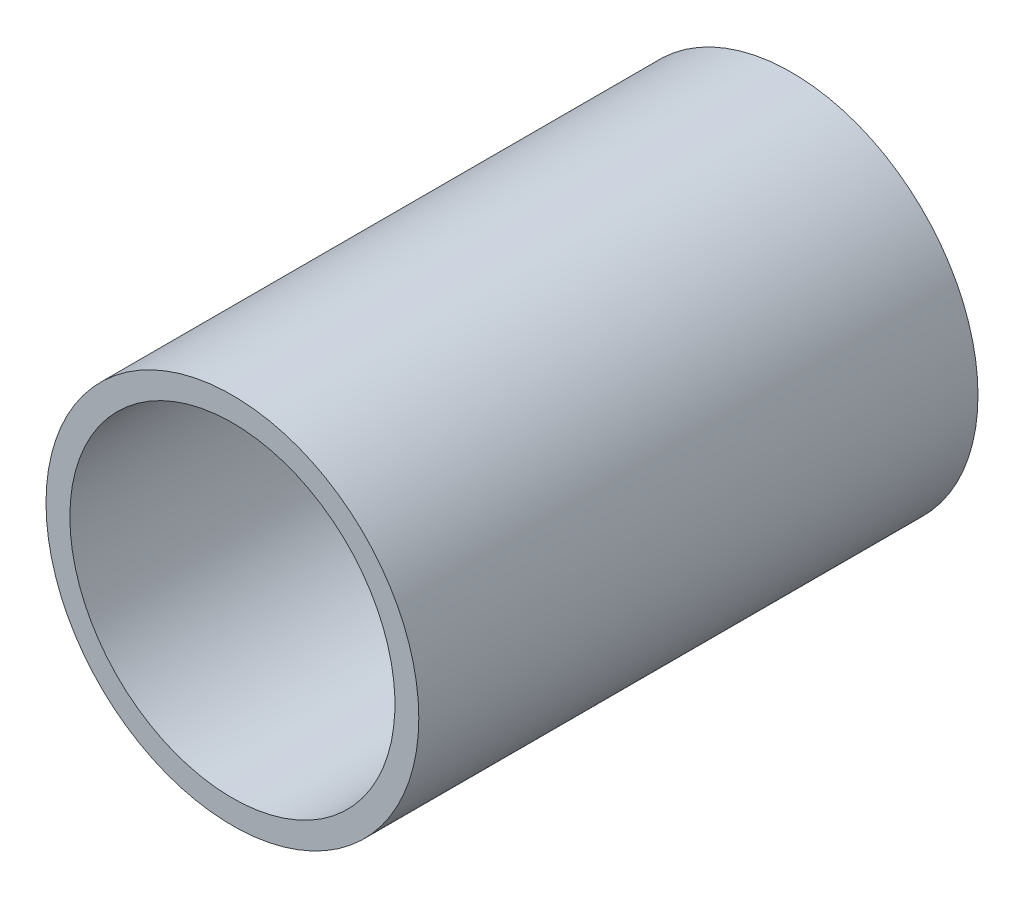
SolidWorks part; units mm, degrees
material "6061 Alloy"
ref_plane "Front Plane" through (0, 0, 0) normal (0, 0, 1) x (1, 0, 0)
ref_plane "Top Plane" through (0, 0, 0) normal (0, 1, 0) x (1, 0, 0)
ref_plane "Right Plane" through (0, 0, 0) normal (1, 0, 0) x (0, 0, -1)
sketch "Sketch1" plane through (0, 0, 0) normal (0, 0, 1) x (1, 0, 0)
  line L0 (-6.35, 0) -> (6.35, 0) construction
  line L1 (0, 0) -> (0, 1.0456) construction
  point P0 (-5.5372, 0)
  point P4 (0, 0)
  point P6 (5.5372, 0)
  dimension "OD" = 12.7
  dimension "ID" = 11.0744
sketch "Sketch2" plane through (0, 0, 0) normal (0, 0, 1) x (1, 0, 0)
  line L0 (-6.35, 0) -> (6.35, 0) construction
  circle A0 centre (0, 0) radius 5.5372
  circle A1 centre (0, 0) radius 6.35
  dimension "D1" = 11.0744
  dimension "D2" = 12.7
extrude "Boss-Extrude1" add sketch "Sketch2" along normal mid plane 19.05
sketch "Sketch3" plane through (0, 0, 0) normal (1, 0, 0) x (0, 0, -1)
  line L0 (9.525, 0) -> (-9.525, 0) construction
  line L1 (-9.525, 6.35) -> (-9.525, -6.35) construction
  line L2 (0, 0) -> (0, 21.8825) construction
  point P0 (-9.4297, 0)
  point P6 (0, 0)
  point P8 (9.4297, 0)
  dimension "D1" = 18.8595
ref_axis "Center Axis 1" through (0, 0, 9.525) along (0, 0, -1)
ref_plane "Contact Plane 1" through (0, 0, 9.525) normal (0, 0, 1) x (1, 0, 0)
ref_plane "Contact Plane 2" through (0, 0, -9.525) normal (0, 0, -1) x (-1, 0, 0)
equation "\"D1@Sketch2\"=\"ID@Sketch1\""
equation "\"D2@Sketch2\"=\"OD@Sketch1\""
equation "\"D1@Sketch3\"=\"Length@Boss-Extrude1\"*0.99"
